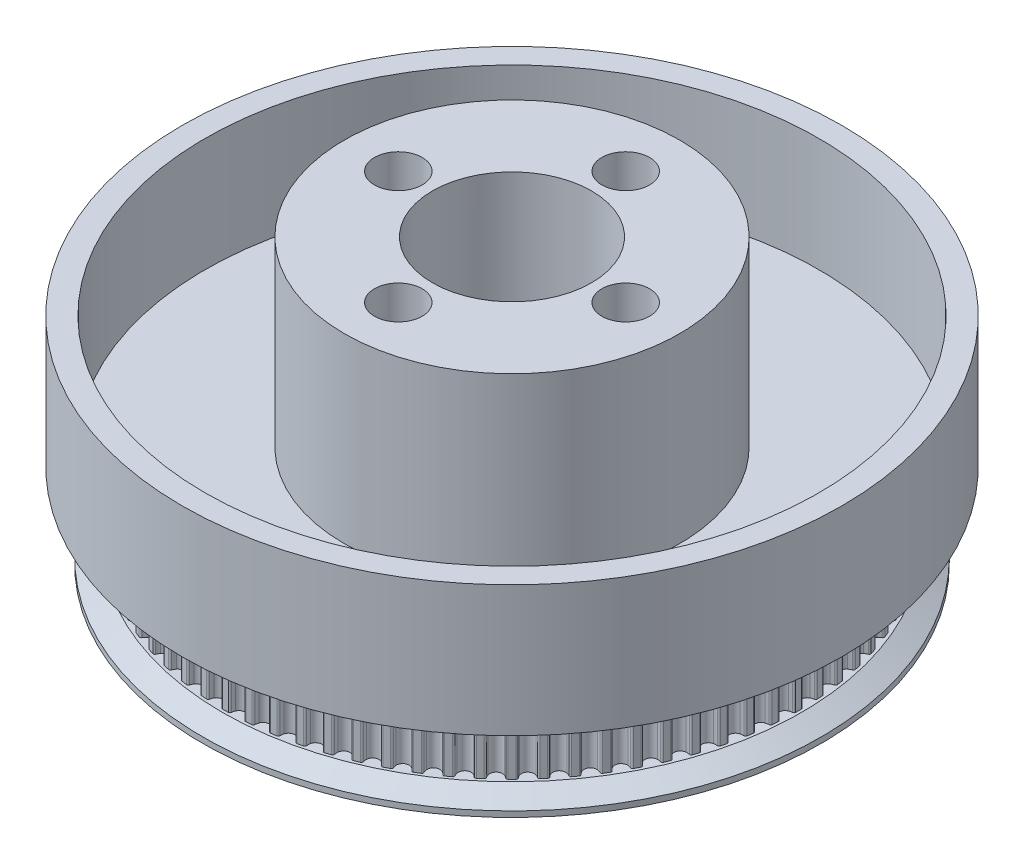
SolidWorks part; units mm, degrees
ref_plane "Front" through (0, 0, 0) normal (0, 0, 1) x (1, 0, 0)
ref_plane "Top" through (0, 0, 0) normal (0, 1, 0) x (1, 0, 0)
ref_plane "Right" through (0, 0, 0) normal (1, 0, 0) x (0, 0, -1)
sketch "Sketch1" plane through (0, 0, 0) normal (0, 1, 0) x (1, 0, 0)
  line L0 (0, 0) -> (0, 25.4648) construction
  line L1 (0, 25.2108) -> (0, 25.8408)
  line L2 (0, 0) -> (0.9997, 25.4452) construction
  line L3 (1.978, 25.1331) -> (2.0274, 25.7611)
  line L4 (1.3894, 25.1757) -> (1.4033, 25.4261) construction
  arc A0 (0.2468, 25.2096) -> (0.3946, 25.0747) centre (0.2453, 25.0596) cw
  arc A1 (0.3946, 25.0747) -> (0.4741, 24.773) centre (1.3894, 25.1757) ccw
  circle A2 centre (0, 0) radius 25.4648 construction
  arc A3 (0.2468, 25.2096) -> (0, 25.2108) centre (0, 0) ccw
  arc A4 (0.9603, 24.4419) -> (0, 24.4608) centre (0, 0) ccw construction
  arc A5 (0.4741, 24.773) -> (1.471, 24.7339) centre (0.9821, 24.9965) ccw
  arc A6 (1.3894, 25.1757) -> (0.9899, 25.1946) centre (0, 0) ccw construction
  arc A7 (0, 25.8408) -> (2.0274, 25.7611) centre (0, 0) cw
  arc A8 (1.574, 25.0284) -> (1.471, 24.7339) centre (0.5901, 25.2071) cw
  arc A9 (1.7319, 25.1512) -> (1.574, 25.0284) centre (1.7216, 25.0016) ccw
  arc A10 (1.7319, 25.1512) -> (1.978, 25.1331) centre (0, 0) cw
  dimension "D1" = 0.15
  dimension "D4" = 50.9296
  dimension "D5" = 1
  dimension "D7" = 0.555
  dimension "D3" = 2.25
  dimension "D8" = 0.75
  dimension "D6" = 0.254
  dimension "D2" = 0.4
  dimension "D9" = 1.38
  dimension "D11" = 0.404
  dimension "D12" = 0.2508
  dimension "D10" = 0.909
sketch "Sketch2" plane through (0, 0, 0) normal (0, 1, 0) x (1, 0, 0)
  circle A0 centre (0, 0) radius 25.4648 construction
  circle A1 centre (0, 0) radius 25.4648
  circle A2 centre (0, 0) radius 7
  dimension "D1" = 14
extrude "Boss-Extrude1" add sketch "Sketch2" along normal mid plane 6
sketch "Sketch6" plane through (0, 0, 0) normal (0, 1, 0) x (1, 0, 0)
  line L0 (0, 25.2008) -> (0, 25.8408)
  line L1 (1.9772, 25.1231) -> (2.0274, 25.7611)
  arc A7 (2.0274, 25.7611) -> (0, 25.8408) centre (0, 0) ccw construction
  arc A8 (2.0274, 25.7611) -> (0, 25.8408) centre (0, 0) ccw
  arc A14 (1.7312, 25.1413) -> (1.5838, 25.0266) centre (1.7216, 25.0016) ccw
  arc A15 (1.4798, 24.7291) -> (1.5838, 25.0266) centre (0.5901, 25.2071) ccw
  arc A16 (0.4649, 24.769) -> (1.4798, 24.7291) centre (0.9821, 24.9965) ccw
  arc A17 (0.3846, 25.0737) -> (0.4649, 24.769) centre (1.3894, 25.1757) ccw
  arc A18 (0.3846, 25.0737) -> (0.2467, 25.1996) centre (0.2453, 25.0596) ccw
  arc A19 (0.2467, 25.1996) -> (0, 25.2008) centre (0, 0) ccw
  arc A20 (1.9772, 25.1231) -> (1.7312, 25.1413) centre (0, 0) ccw
  arc A21 (1.7312, 25.1413) -> (1.5838, 25.0266) centre (1.7216, 25.0016) ccw
  arc A22 (1.4798, 24.7291) -> (1.5838, 25.0266) centre (0.5901, 25.2071) ccw
  arc A23 (0.4649, 24.769) -> (1.4798, 24.7291) centre (0.9821, 24.9965) ccw
  arc A24 (0.3846, 25.0737) -> (0.4649, 24.769) centre (1.3894, 25.1757) ccw
  arc A25 (0.3846, 25.0737) -> (0.2467, 25.1996) centre (0.2453, 25.0596) ccw
  arc A26 (0.2467, 25.1996) -> (0, 25.2008) centre (0, 0) ccw
  arc A27 (1.9772, 25.1231) -> (1.7312, 25.1413) centre (0, 0) ccw
extrude "Cut-Extrude3" cut sketch "Sketch6" against normal through all both and the other way through all
pattern_circular "CirPattern3" count 80 over 360 about axis through (0, 3, 0) along (0, -1, 0) of "Cut-Extrude3"
sketch "Sketch3" plane through (0, 0, 0) normal (0, 0, 1) x (1, 0, 0)
  line L0 (0, 0) -> (0, 9.5108) construction
  line L1 (-25.4648, 3) -> (-27.1968, 4)
  line L2 (-27.1968, 4) -> (-27.1968, 4.5)
  line L3 (-27.1968, 4.5) -> (-7, 4.5)
  line L4 (-7, 4.5) -> (-7, 3)
  line L5 (-7, 3) -> (-25.4648, 3)
  line L6 (7, 3) -> (-7, 3) construction
  dimension "D4" = 50.9296
  dimension "D1" = 1.5
  dimension "D2" = 0.5
  dimension "D3" = 30
revolve "Revolve1" add sketch "Sketch3" angle 360 about L0
mirror "Mirror1" about plane through (0, 0, 0) normal (0, 1, 0) of "Revolve1"
sketch "Sketch4" plane through (0, 0, 0) normal (0, 0, 1) x (1, 0, 0)
  line L0 (0, 0) -> (0, 14.0175) construction
  line L1 (27.1968, 4.5) -> (-27.1968, 4.5) construction
  line L2 (-7, 4.5) -> (-13.5, 4.5)
  line L3 (-7, 4.5) -> (-7, 10.5)
  line L4 (-7, 10.5) -> (-13.5, 10.5)
  line L5 (-13.5, 4.5) -> (-13.5, 10.5)
  dimension "D2" = 6
  dimension "D1" = 6.5
revolve "Revolve2" add sketch "Sketch4" angle 360 about L0
sketch "Sketch5" plane through (0, 0, 0) normal (0, 0, 1) x (1, 0, 0)
  line L1 (0, 4.5) -> (0, 10.5) construction
  line L2 (13.5, 10.5) -> (-13.5, 10.5) construction
  line L7 (-13.5, 10.5) -> (-13.5, 4.5) construction
  line L8 (-13.5, 10.5) -> (-13.5, 4.5) construction
  circle A0 centre (0, 7.5) radius 1.6
  dimension "D1" = 3.2
extrude "Cut-Extrude2" cut sketch "Sketch5" along normal through all
pattern_circular "CirPattern2" count 2 over 90 about axis through (0, 3, 0) along (0, -1, 0) of "Cut-Extrude2" reverse direction yes
sketch "Esboço1" plane through (0, 4.5, 0) normal (0, 1, 0) x (1, 0, 0)
  circle A0 centre (0, 0) radius 14.75
  circle A1 centre (0, 10) radius 1.5823
  circle A2 centre (0, 0) radius 7
  circle A3 centre (10, 0) radius 1.5823
  circle A4 centre (0, -10) radius 1.5823
  circle A5 centre (-10, 0) radius 1.5823
  point P15 (0, 0)
  dimension "D1" = 29.5
  dimension "D2" = 10
  dimension "D3" = 14
  dimension "D4" = 4
extrude "Ressalto-extrusão1" add sketch "Esboço1" along normal blind 16
sketch "Esboço3" plane through (0, 3, 0) normal (0, -1, 0) x (1, 0, 0)
  circle A0 centre (0, 0) radius 26 construction
  circle A1 centre (0, 0) radius 29
  circle A2 centre (0, 0) radius 7
  dimension "D1" = 52
  dimension "D2" = 58
extrude "Ressalto-extrusão2" add sketch "Esboço3" against normal up to surface (1.5 mm away) up to face at (0, 4.5, -14.75)
sketch "Esboço4" plane through (0, 4.5, 0) normal (0, 1, 0) x (1, 0, 0)
  circle A0 centre (0, 0) radius 29
  circle A1 centre (0, 0) radius 27
  dimension "D1" = 54
extrude "Ressalto-extrusão3" add sketch "Esboço4" along normal blind 10
sketch "Esboço2" plane through (0, 20.5, 0) normal (0, 1, 0) x (1, 0, 0)
  circle A0 centre (0, 10) radius 2.1
  circle A1 centre (10, 0) radius 2.1
  circle A2 centre (0, -10) radius 2.1
  circle A3 centre (-10, 0) radius 2.1
  point P12 (0, 0)
  dimension "D2" = 4.2
  dimension "D1" = 4
extrude "Corte-extrusão1" cut sketch "Esboço2" against normal through all
equation "\"belt-step\"= 2"
equation "\"pulley-teeth\"= 80"
equation "\"pulley-dia\"= ( \"belt-step\" * \"pulley-teeth\" ) / Pi"
equation "\"D3@Sketch1\"=(360/\"pulley-teeth\")/2"
equation "\"D4@Sketch1\"=\"pulley-dia\""
equation "\"bore-dia\"= 14"
equation "\"belt-thick\"= 6"
equation "\"D4@Sketch3\"=\"pulley-dia\""
equation "\"D1@Sketch2\"=\"bore-dia\""
equation "\"D1@Boss-Extrude1\"=\"belt-thick\""
equation "\"teeth-offset\"= 0.01"
equation "\"D1@Sketch6\"=\"teeth-offset\""
equation "\"D1@CirPattern3\"=\"pulley-teeth\""
equation "\"flange-wall\"= 6.5"
equation "\"D1@Sketch4\"=\"flange-wall\""
equation "\"flange-h\"= 6"
equation "\"screw-dia\"= 3.2"
equation "\"D2@Sketch4\"=\"flange-h\""
equation "\"D1@Sketch5\"=\"screw-dia\""
equation "\"D10@Sketch1\"=(0.4/(Pi*(\"pulley-dia\"-(2*\"D12@Sketch1\"))))*360"
